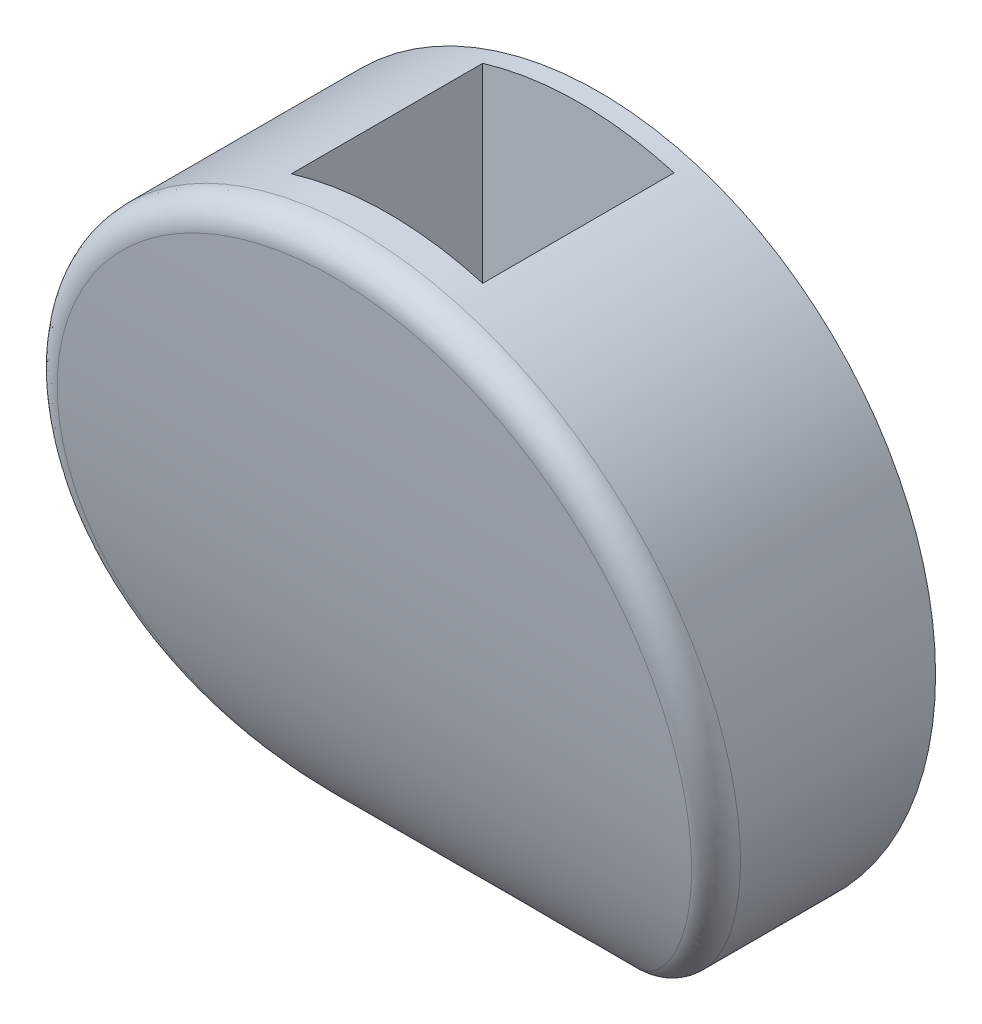
SolidWorks part; units mm, degrees
ref_plane "Plan de face" through (0, 0, 0) normal (0, 0, 1) x (1, 0, 0)
ref_plane "Plan de dessus" through (0, 0, 0) normal (0, 1, 0) x (1, 0, 0)
ref_plane "Plan de droite" through (0, 0, 0) normal (1, 0, 0) x (0, 0, -1)
sketch "Esquisse1" plane through (0, 0, 0) normal (0, 0, 1) x (1, 0, 0)
  circle A0 centre (0.2907, 0.2907) radius 67
  dimension "D1" = 134
extrude "Boss.-Extru.1" add sketch "Esquisse1" along normal blind 53.34
sketch "Esquisse4" plane through (0, 0, 0) normal (1, 0, 0) x (0, 0, -1)
  line L1 (-0.1422, -67.1272) -> (-53.34, -66.7093)
  line L2 (-53.34, -66.7093) -> (-53.34, 67.2907)
  spline S0 degree 3 poles (-53.34, 67.2907) (-53.3149, 64.9653) (-44.6519, -34.8903) (-23.1604, -66.3734) (-0.1422, -67.1272) knots 0 0 0 0 0.36297 1 1 1 1
extrude "Enlèv. mat.-Extru.1" cut sketch "Esquisse4" against normal through all both and the other way through all
fillet "Congé1" radius 5 1 edges at (-0.0427, -66.7085, 4.6747)
sketch "Esquisse5" plane through (0, 0, 0) normal (0, 1, 0) x (1, 0, 0)
  line L0 (67.2907, -40.0395) -> (67.2907, 0) construction
  line L1 (67.2907, 0) -> (-66.7093, 0) construction
  line L2 (-19.05, -3.81) -> (19.05, -3.81)
  line L3 (-19.05, -3.81) -> (-19.05, -41.91)
  line L4 (-19.05, -41.91) -> (19.05, -41.91)
  line L5 (19.05, -3.81) -> (19.05, -41.91)
  dimension "D1" = 3.81
  dimension "D2" = 48.2407
  dimension "D3" = 38.1
  dimension "D4" = 38.1
extrude "Enlèv. mat.-Extru.2" cut sketch "Esquisse5" along normal up to next and the other way blind 3.81
